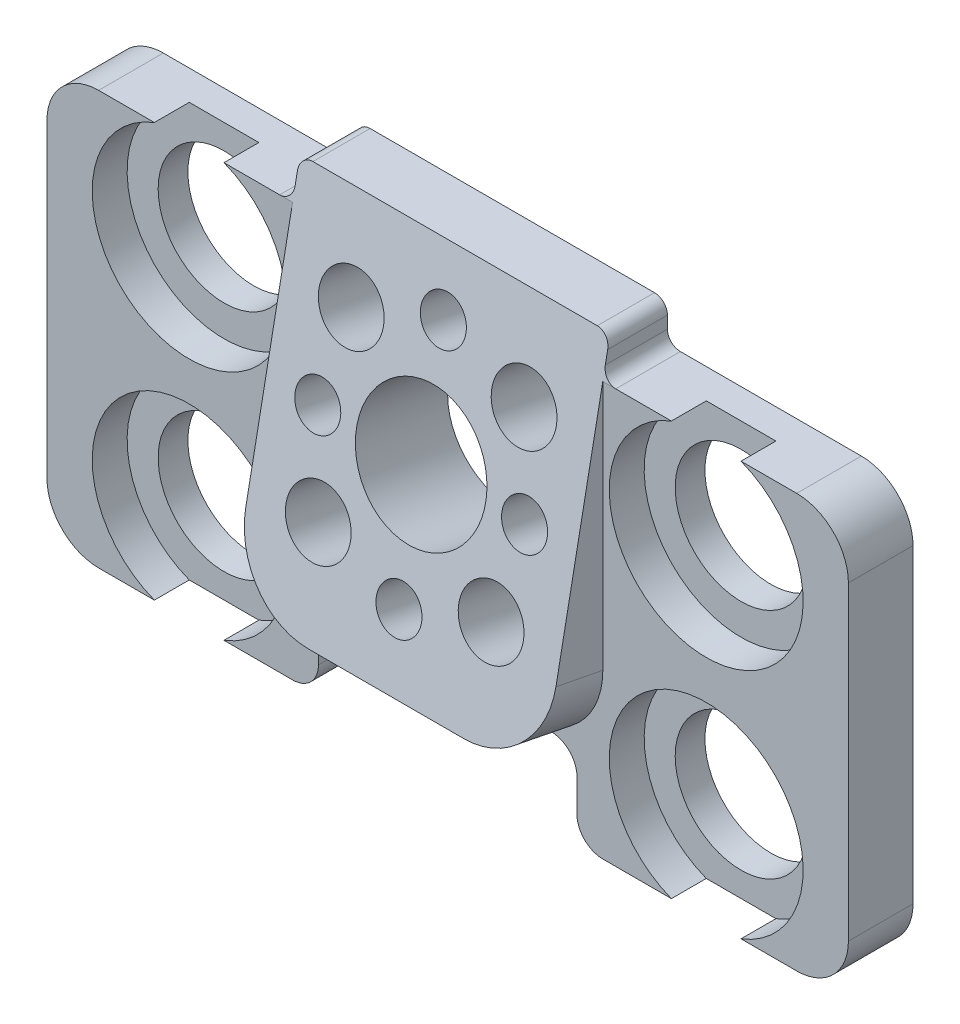
SolidWorks part; units mm, degrees
ref_plane "Front Plane" through (0, 0, 0) normal (0, 0, 1) x (1, 0, 0)
ref_plane "Top Plane" through (0, 0, 0) normal (0, 1, 0) x (1, 0, 0)
ref_plane "Right Plane" through (0, 0, 0) normal (1, 0, 0) x (0, 0, -1)
sketch "Sketch1" plane through (0, 0, 0) normal (0, 0, 1) x (1, 0, 0)
  line L0 (0, 0) -> (0, 4.7239) construction
  line L1 (-27, -16) -> (27, -16)
  line L2 (-31, -12) -> (-31, 12)
  line L3 (-27, 16) -> (27, 16)
  line L4 (31, -12) -> (31, 12)
  line L5 (-31, -16) -> (31, 16) construction
  line L6 (-31, 16) -> (31, -16) construction
  line L7 (0, 0) -> (15.0819, 0) construction
  arc A0 (27, -16) -> (31, -12) centre (27, -12) ccw
  arc A1 (-31, 12) -> (-27, 16) centre (-27, 12) cw
  arc A2 (-27, -16) -> (-31, -12) centre (-27, -12) cw
  arc A3 (27, 16) -> (31, 12) centre (27, 12) cw
  circle A4 centre (-20, 9) radius 4.9 construction
  circle A5 centre (20, 9) radius 4.9 construction
  circle A6 centre (-20, -9) radius 4.9 construction
  circle A7 centre (20, -9) radius 4.9 construction
  circle A8 centre (-8, 0) radius 1.7 construction
  circle A9 centre (8, 0) radius 1.7 construction
  circle A10 centre (0, 9.5) radius 1.7 construction
  circle A11 centre (0, -9.5) radius 1.7 construction
  circle A12 centre (0, 0) radius 5 construction
  circle A13 centre (0, 0) radius 13.75 construction
  circle A14 centre (-20, 9) radius 5.1
  circle A15 centre (20, -9) radius 5.1
  circle A16 centre (-20, -9) radius 5.1
  circle A17 centre (20, 9) radius 5.1
  point P0 (0, 0)
  dimension "D3" = 4
  dimension "D4" = 9.8
  dimension "D7" = 3.4
  dimension "D10" = 10
  dimension "D11" = 27.5
  dimension "D2" = 7
  dimension "D5" = 20
  dimension "D6" = 9
  dimension "D8" = 8
  dimension "D9" = 19
  dimension "D12" = 11
  dimension "D15" = 7
  dimension "D13" = 0.2
  dimension "D14" = 0.2
extrude "Boss-Extrude1" add sketch "Sketch1" along normal blind 5 contours A3 L3 A1 L2 A2 L1 A0 L4 A11 A10 A6 A4 A5 A7 A8 A9 region at (0, 0, 0)
sketch "Sketch2" plane through (0, 0, 0) normal (0, 0, -1) x (-1, 0, 0)
  line L0 (0, 0) -> (0, 16.6872) construction
  line L1 (0, 0) -> (21.6404, 0) construction
  circle A0 centre (20, 9) radius 7.5
  circle A1 centre (-20, 9) radius 7.5
  circle A2 centre (-20, -9) radius 7.5
  circle A3 centre (20, -9) radius 7.5
  circle A8 centre (20, 9) radius 5.1 construction
  dimension "D1" = 15
extrude "Cut-Extrude1" cut sketch "Sketch2" against normal through all from offset 2.3 offset against normal yes
sketch "Sketch3" plane through (0, 0, 0) normal (1, 0, 0) x (0, 0, -1)
  line L0 (-5, 16) -> (-5, -16)
  line L1 (-5, 16) -> (-5, -9.4679)
  line L2 (-5, 16) -> (-9.7702, -8.5407)
  line L3 (-5, 16) -> (-4.4276, 18.9449)
  line L4 (-9.7702, -8.5407) -> (-5, -9.4679)
  line L5 (-4.4276, 18.9449) -> (0, 18.9449)
  line L6 (0, 18.9449) -> (0, 16)
  line L7 (0, 16) -> (-5, 16)
  dimension "D1" = 11
  dimension "D2" = 25
  dimension "D3" = 3
extrude "Boss-Extrude2" add sketch "Sketch3" along normal mid plane 24 contours L2 L4 L1 | L7 L6 L5 L3 region at (0, -0.6695, 6.5901) region at (0, 17.4426, 2.3598)
sketch "Sketch4" plane through (0, 1.519, 7.8148) normal (0, 0.1908, 0.9816) x (1, 0, 0)
  line L0 (0, 0) -> (0, 8) construction
  line L1 (0, 4) -> (-4.4952, 4) construction
  line L2 (0, 4) -> (-16.6746, -12.6746) construction
  circle A0 centre (0, 4) radius 5
  circle A1 centre (0, 13) radius 1.75
  circle A2 centre (8, 4) radius 1.75
  circle A3 centre (0, -5) radius 1.75
  circle A4 centre (-8, 4) radius 1.75
  circle A5 centre (-6.6862, -2.6862) radius 2.5
  circle A6 centre (6.6862, -2.6862) radius 2.5
  circle A7 centre (6.6862, 10.6862) radius 2.5
  circle A8 centre (-6.6862, 10.6862) radius 2.5
  point P13 (0, 4)
  point P16 (0, 4)
  dimension "D1" = 10
  dimension "D2" = 3.5
  dimension "D8" = 5
  dimension "D3" = 9
  dimension "D4" = 8
  dimension "D7" = 4
  dimension "D9" = 45
  dimension "D5" = 2
  dimension "D6" = 2
extrude "Cut-Extrude2" cut sketch "Sketch4" against normal through all
fillet "Fillet1" radius 1 4 edges at (12, 18.9449, 2.2138) (-12, 18.9449, 2.2138)
sketch "Sketch5" plane through (0, 0, 5) normal (0, 0, 1) x (1, 0, 0)
  line L0 (12, -9.4679) -> (-12, -9.4679) construction
  line L2 (-10, -9.4679) -> (10, -9.4679)
  line L5 (-17.3074, -16) -> (17.3074, -16) construction
  line L6 (10, -16) -> (-10, -16)
  line L7 (-10, -9.4679) -> (-10, -16)
  line L8 (0, 0) -> (0, -25.1949) construction
  line L9 (10, -9.4679) -> (10, -16)
  dimension "D1" = 20
extrude "Cut-Extrude3" cut sketch "Sketch5" against normal through all
fillet "Fillet2" radius 2 4 edges at (10, -16, 2.5) (10, -9.4679, 2.5) (-10, -9.4679, 2.5) (-10, -16, 2.5)
fillet "Fillet3" radius 6 2 edges at (12, -9.0043, 7.3851) (-12, -9.0043, 7.3851)
equation "\"printer_offset\"= .2mm"
equation "\"D13@Sketch1\"=\"printer_offset\""
equation "\"D14@Sketch1\"=\"printer_offset\""
